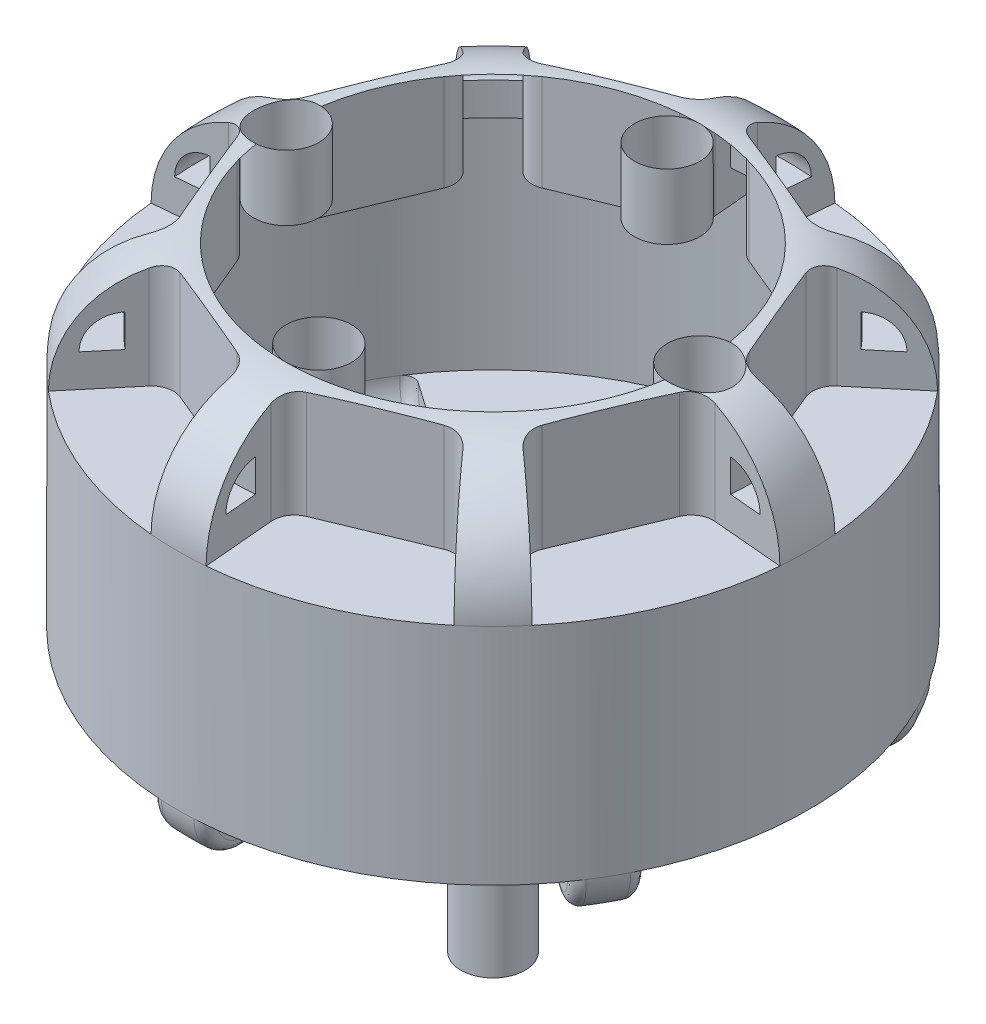
SolidWorks part; units mm, degrees
ref_plane "前视基准面" through (0, 0, 0) normal (0, 0, 1) x (1, 0, 0)
ref_plane "上视基准面" through (0, 0, 0) normal (0, 1, 0) x (1, 0, 0)
ref_plane "右视基准面" through (0, 0, 0) normal (1, 0, 0) x (0, 0, -1)
sketch "草图1" plane through (0, 0, 0) normal (0, 0, 1) x (1, 0, 0)
  line L0 (0, 0) -> (0, 5)
  line L1 (0, 5) -> (9.5, 5)
  line L2 (14.5, 0) -> (0, 0)
  line L3 (12, 3) -> (12, 1.5)
  line L4 (12, 1.5) -> (13.5, 1.5)
  arc A0 (9.5, 5) -> (14.5, 0) centre (9.5, 0) cw
  arc A1 (13.5, 1.5) -> (12, 3) centre (12, 1.5) ccw
  dimension "D1" = 14.5
  dimension "D4" = 12
  dimension "D2" = 9.5
  dimension "D3" = 5
  dimension "D5" = 1.5
  dimension "D6" = 1.5
revolve "旋转1" add sketch "草图1" angle 360 about L0
sketch "草图2" plane through (0, 0, 0) normal (0, -1, 0) x (1, 0, 0)
  line L0 (0, 0) -> (0, -14.5) construction
  line L1 (-1.2638, -14.4448) -> (-0.9138, -10.4448)
  line L2 (-9.3204, -11.1076) -> (-6.7394, -8.0318)
  line L3 (-6.7394, -8.0318) -> (-0.9138, -10.4448)
  line L4 (-11.1076, -9.3204) -> (-8.0318, -6.7394)
  line L5 (-14.4448, -1.2638) -> (-10.4448, -0.9138)
  line L6 (-10.4448, -0.9138) -> (-8.0318, -6.7394)
  line L7 (-14.4448, 1.2638) -> (-10.4448, 0.9138)
  line L8 (-11.1076, 9.3204) -> (-8.0318, 6.7394)
  line L9 (-8.0318, 6.7394) -> (-10.4448, 0.9138)
  line L10 (-9.3204, 11.1076) -> (-6.7394, 8.0318)
  line L11 (-1.2638, 14.4448) -> (-0.9138, 10.4448)
  line L12 (-0.9138, 10.4448) -> (-6.7394, 8.0318)
  line L13 (1.2638, 14.4448) -> (0.9138, 10.4448)
  line L14 (9.3204, 11.1076) -> (6.7394, 8.0318)
  line L15 (6.7394, 8.0318) -> (0.9138, 10.4448)
  line L16 (11.1076, 9.3204) -> (8.0318, 6.7394)
  line L17 (14.4448, 1.2638) -> (10.4448, 0.9138)
  line L18 (10.4448, 0.9138) -> (8.0318, 6.7394)
  line L19 (14.4448, -1.2638) -> (10.4448, -0.9138)
  line L20 (11.1076, -9.3204) -> (8.0318, -6.7394)
  line L21 (8.0318, -6.7394) -> (10.4448, -0.9138)
  line L22 (9.3204, -11.1076) -> (6.7394, -8.0318)
  line L23 (1.2638, -14.4448) -> (0.9138, -10.4448)
  line L24 (0.9138, -10.4448) -> (6.7394, -8.0318)
  circle A0 centre (0, 0) radius 14.5 construction
  arc A1 (-1.2638, -14.4448) -> (-9.3204, -11.1076) centre (0, 0) cw
  arc A2 (-11.1076, -9.3204) -> (-14.4448, -1.2638) centre (0, 0) cw
  arc A3 (-14.4448, 1.2638) -> (-11.1076, 9.3204) centre (0, 0) cw
  arc A4 (-9.3204, 11.1076) -> (-1.2638, 14.4448) centre (0, 0) cw
  arc A5 (1.2638, 14.4448) -> (9.3204, 11.1076) centre (0, 0) cw
  arc A6 (11.1076, 9.3204) -> (14.4448, 1.2638) centre (0, 0) cw
  arc A7 (14.4448, -1.2638) -> (11.1076, -9.3204) centre (0, 0) cw
  arc A8 (9.3204, -11.1076) -> (1.2638, -14.4448) centre (0, 0) cw
  point P42 (0, 0)
  dimension "D4" = 14.5
  dimension "D1" = 5
  dimension "D2" = 35
  dimension "D3" = 4
  dimension "D5" = 8
extrude "切除-拉伸1" cut sketch "草图2" against normal blind 5.5
fillet "圆角1" radius 1 16 edges at (0.9138, 2.451, 10.4448) (6.7394, 2.451, 8.0318) (8.0318, 2.451, 6.7394) (10.4448, 2.451, 0.9138) (10.4448, 2.451, -0.9138) (8.0318, 2.451, -6.7394) (6.7394, 2.451, -8.0318) (0.9138, 2.451, -10.4448) (-0.9138, 2.451, -10.4448) (-6.7394, 2.451, -8.0318) (-8.0318, 2.451, -6.7394) (-10.4448, 2.451, -0.9138) (-10.4448, 2.451, 0.9138) (-8.0318, 2.451, 6.7394) (-6.7394, 2.451, 8.0318) (-0.9138, 2.451, 10.4448)
sketch "草图3" plane through (0, 0, 0) normal (0, -1, 0) x (1, 0, 0)
  circle A0 centre (0, 0) radius 14.5
extrude "凸台-拉伸1" add sketch "草图3" along normal blind 12.3
sketch "草图4" plane through (0, 5, 0) normal (0, 1, 0) x (1, 0, 0)
  circle A0 centre (0, 8) radius 1.5
  circle A1 centre (0, -8) radius 1.5
  circle A2 centre (-9.5, 0) radius 1.5
  circle A3 centre (9.5, 0) radius 1.5
  dimension "D1" = 8
  dimension "D5" = 3
  dimension "D2" = 8
  dimension "D3" = 9.5
  dimension "D4" = 9.5
extrude "切除-拉伸2" cut sketch "草图4" against normal blind 3
sketch "草图6" plane through (0, -12.3, 0) normal (0, -1, 0) x (1, 0, 0)
  line L0 (1.2638, 14.4448) -> (0.7388, 8.4448)
  line L1 (0.7388, 8.4448) -> (6.944, 4.8623)
  line L2 (6.944, 4.8623) -> (11.8777, 8.3169)
  line L3 (0, 0) -> (0, 14.5) construction
  line L4 (7.6828, -3.5826) -> (13.1415, -6.128)
  line L5 (7.6828, 3.5826) -> (7.6828, -3.5826)
  line L6 (13.1415, 6.128) -> (7.6828, 3.5826)
  line L7 (0.7388, -8.4448) -> (1.2638, -14.4448)
  line L8 (6.944, -4.8623) -> (0.7388, -8.4448)
  line L9 (11.8777, -8.3169) -> (6.944, -4.8623)
  line L10 (-6.944, -4.8623) -> (-11.8777, -8.3169)
  line L11 (-0.7388, -8.4448) -> (-6.944, -4.8623)
  line L12 (-1.2638, -14.4448) -> (-0.7388, -8.4448)
  line L13 (-7.6828, 3.5826) -> (-13.1415, 6.128)
  line L14 (-7.6828, -3.5826) -> (-7.6828, 3.5826)
  line L15 (-13.1415, -6.128) -> (-7.6828, -3.5826)
  line L16 (-0.7388, 8.4448) -> (-1.2638, 14.4448)
  line L17 (-6.944, 4.8623) -> (-0.7388, 8.4448)
  line L18 (-11.8777, 8.3169) -> (-6.944, 4.8623)
  circle A0 centre (0, 0) radius 14.5 construction
  arc A1 (11.8777, 8.3169) -> (1.2638, 14.4448) centre (0, 0) ccw
  arc A2 (13.1415, -6.128) -> (13.1415, 6.128) centre (0, 0) ccw
  arc A3 (1.2638, -14.4448) -> (11.8777, -8.3169) centre (0, 0) ccw
  arc A4 (-11.8777, -8.3169) -> (-1.2638, -14.4448) centre (0, 0) ccw
  arc A5 (-13.1415, 6.128) -> (-13.1415, -6.128) centre (0, 0) ccw
  arc A6 (-1.2638, 14.4448) -> (-11.8777, 8.3169) centre (0, 0) ccw
  point P34 (0, 0)
  dimension "D4" = 14.5
  dimension "D1" = 5
  dimension "D2" = 50
  dimension "D3" = 6
  dimension "D5" = 6
extrude "切除-拉伸3" cut sketch "草图6" against normal blind 2
fillet "圆角4" radius 2 6 edges at (0, -12.3, 14.5) (12.5574, -12.3, 7.25) (12.5574, -12.3, -7.25) (0, -12.3, -14.5) (-12.5574, -12.3, -7.25) (-12.5574, -12.3, 7.25)
fillet "圆角2" radius 0.5 24 edges at (9.5058, -12.3, 4.4326) (8.5917, -12.3, 6.016) (9.5058, -12.3, -4.4326) (8.5917, -12.3, -6.016) (0.9141, -12.3, -10.4486) (-0.9141, -12.3, -10.4486) (-8.5917, -12.3, -6.016) (-9.5058, -12.3, -4.4326) (-9.5058, -12.3, 4.4326) (-8.5917, -12.3, 6.016) (0.9141, -12.3, 10.4486) (-0.9141, -12.3, 10.4486) (12.6106, -11.7142, 5.8804) (11.3979, -11.7142, 7.9809) (12.6106, -11.7142, -5.8804) (11.3979, -11.7142, -7.9809) (1.2127, -11.7142, -13.8613) (-1.2127, -11.7142, -13.8613) (-11.3979, -11.7142, -7.9809) (-12.6106, -11.7142, -5.8804) (-12.6106, -11.7142, 5.8804) (-11.3979, -11.7142, 7.9809) (1.2127, -11.7142, 13.8613) (-1.2127, -11.7142, 13.8613)
sketch "草图7" plane through (0, -12.3, 0) normal (0, -1, 0) x (1, 0, 0)
  circle A0 centre (0, 0) radius 1.475
  dimension "D1" = 2.95
extrude "凸台-拉伸2" add sketch "草图7" along normal blind 10.9
sketch "草图8" plane through (0, -12.3, 0) normal (0, -1, 0) x (1, 0, 0)
  circle A1 centre (0, 0) radius 5.15 construction
  circle A2 centre (5.15, 0) radius 1
  circle A3 centre (-2.575, -4.46) radius 1
  circle A4 centre (-2.575, 4.46) radius 1
  point P11 (0, 0)
  dimension "D1" = 10.3
  dimension "D2" = 2
  dimension "D3" = 3
extrude "切除-拉伸4" cut sketch "草图8" against normal blind 3
